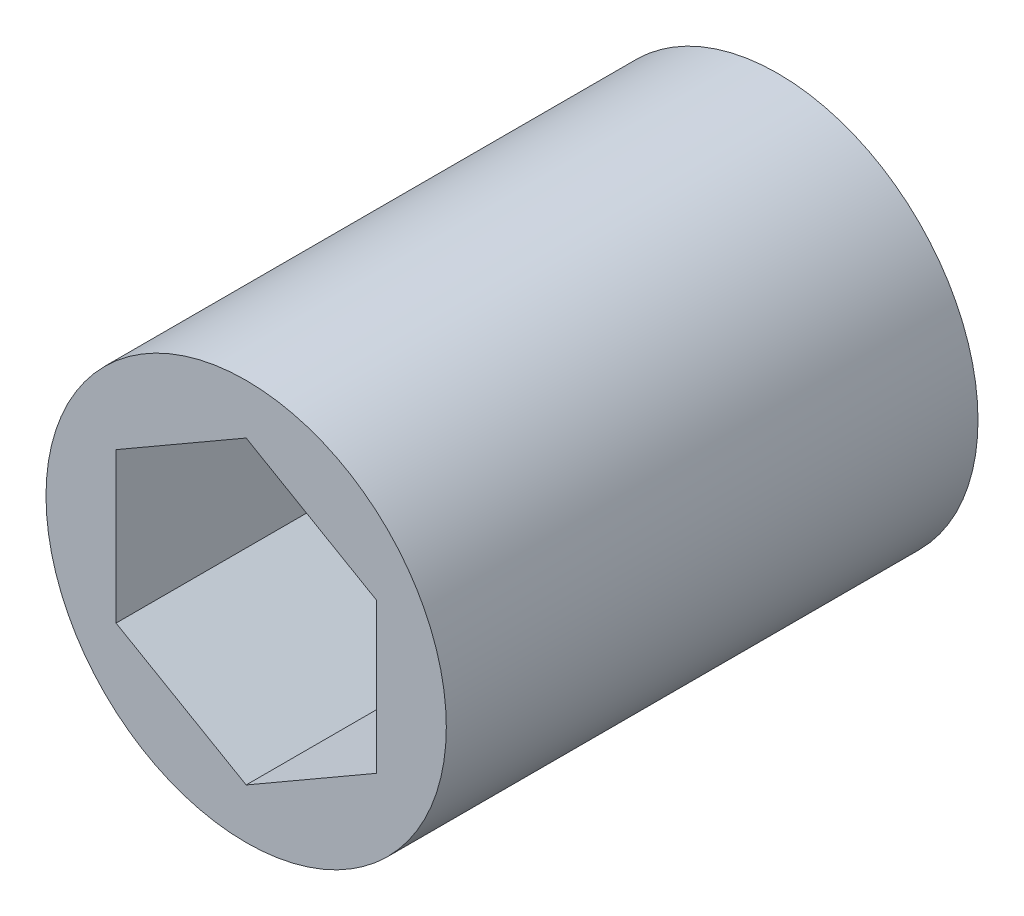
SolidWorks part; units mm, degrees
material "PET"
ref_plane "Front Plane" through (0, 0, 0) normal (0, 0, 1) x (1, 0, 0)
ref_plane "Top Plane" through (0, 0, 0) normal (0, 1, 0) x (1, 0, 0)
ref_plane "Right Plane" through (0, 0, 0) normal (1, 0, 0) x (0, 0, -1)
sketch "Sketch1" plane through (0, 0, 0) normal (0, 0, 1) x (1, 0, 0)
  line L1 (6.604, 3.8128) -> (0, 7.6256)
  line L2 (0, 7.6256) -> (-6.604, 3.8128)
  line L3 (-6.604, 3.8128) -> (-6.604, -3.8128)
  line L4 (-6.604, -3.8128) -> (0, -7.6256)
  line L5 (0, -7.6256) -> (6.604, -3.8128)
  line L6 (6.604, -3.8128) -> (6.604, 3.8128)
  circle A0 centre (0, 0) radius 6.604 construction
  circle A1 centre (0, 0) radius 10.16
  dimension "D1" = 13.208
  dimension "D2" = 20.32
extrude "Boss-Extrude1" add sketch "Sketch1" along normal blind 26.9875
ref_axis "Axis1" through (0, 0, 26.9875) along (0, 0, -1)
